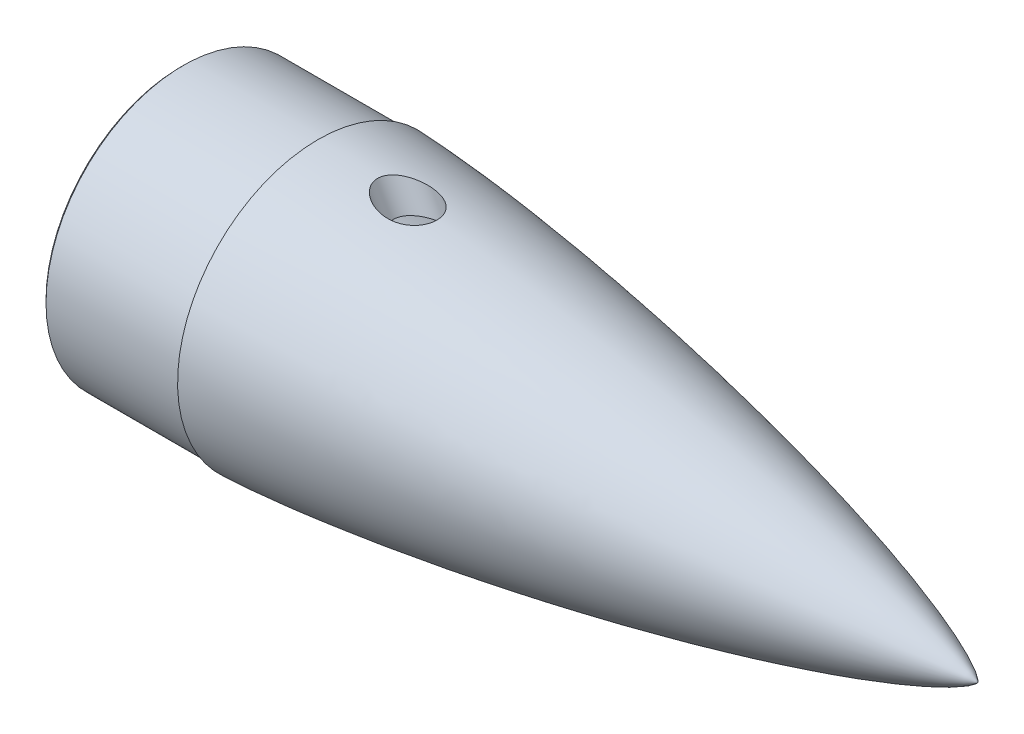
SolidWorks part; units mm, degrees
material "Plain Carbon Steel"
ref_plane "Front Plane" through (0, 0, 0) normal (0, 0, 1) x (1, 0, 0)
ref_plane "Top Plane" through (0, 0, 0) normal (0, 1, 0) x (1, 0, 0)
ref_plane "Right Plane" through (0, 0, 0) normal (1, 0, 0) x (0, 0, -1)
ref_axis "Axis1" through (46.9179, 0, 0) along (-1, 0, 0)
sketch "Sketch10" plane through (0, 0, 0) normal (0, 0, 1) x (1, 0, 0)
  line L1 (-1.0327, 0) -> (486.9547, 0) construction
  line L2 (11.1125, 81.9998) -> (11.1125, 67.4998)
  line L3 (11.1125, 81.9998) -> (-84.6045, 81.9998)
  line L4 (408.9673, 0) -> (368.9673, 0)
  line L5 (-84.6045, 81.9998) -> (-84.6045, 84.9998)
  line L6 (-84.6045, 84.9998) -> (0.3953, 84.9998)
  line L7 (0.3953, 84.9998) -> (0.3953, 86.9998)
  line L8 (11.1125, 67.4998) -> (129.3045, 67.4998)
  line L9 (46.9179, 0) -> (-46.1272, 0) construction
  spline S0 degree 4 poles (408.9673, 0) (408.9649, 0.0135) (408.958, 0.0399) (408.9365, 0.0905) (408.8922, 0.1741) (408.8263, 0.2756) (408.7217, 0.4158) (408.5611, 0.6051) (408.3056, 0.8724) (407.8697, 1.2753) (407.121, 1.8851) (405.8038, 2.8259) (403.4624, 4.2872) (399.3253, 6.5318) (392.4811, 9.7589) (380.6621, 14.628) (363.6372, 20.7117) (342.2152, 27.4765) (317.4285, 34.4976) (291.8793, 41.1048) (266.2105, 47.229) (240.4455, 52.9334) (214.5989, 58.2554) (188.6809, 63.2176) (165.9462, 67.2533) (146.422, 70.4938) (130.1279, 73.0449) (117.0786, 74.9942) (104.0155, 76.8485) (92.5733, 78.3845) (82.7571, 79.6356) (74.5713, 80.6322) (68.0193, 81.4008) (61.4637, 82.1394) (54.9047, 82.8464) (48.3422, 83.5199) (41.7761, 84.1578) (36.0275, 84.6822) (31.0979, 85.1052) (26.9883, 85.4387) (23.6997, 85.6932) (20.0858, 85.9584) (16.7199, 86.189) (13.6021, 86.387) (10.7327, 86.5546) (8.4366, 86.6787) (6.14, 86.7922) (4.1299, 86.8793) (2.4065, 86.9446) (1.2573, 86.979) (0.6827, 86.9949) (0.3953, 86.9998) knots 0 0 0 0 0 0.00013 0.00026 0.00052 0.0009 0.00128 0.001925 0.002882 0.004418 0.006927 0.011111 0.018279 0.030673 0.051704 0.083102 0.139909 0.202703 0.265496 0.32829 0.391083 0.453877 0.516671 0.579464 0.642258 0.673655 0.705051 0.736448 0.767845 0.799242 0.81494 0.830639 0.846337 0.862036 0.877734 0.893432 0.909131 0.924829 0.932678 0.940527 0.948377 0.956226 0.967169 0.972641 0.978113 0.983585 0.989056 0.994528 0.997264 1 1 1 1 1 construction
  spline S1 degree 4 poles (408.9673, 0) (408.9649, 0.0135) (408.958, 0.0399) (408.9365, 0.0905) (408.8922, 0.1741) (408.8263, 0.2756) (408.7217, 0.4158) (408.5611, 0.6051) (408.3056, 0.8724) (407.8697, 1.2753) (407.121, 1.8851) (405.8038, 2.8259) (403.4624, 4.2872) (399.3253, 6.5318) (392.4811, 9.7589) (380.6621, 14.628) (363.6372, 20.7117) (342.2152, 27.4765) (317.4285, 34.4976) (291.8793, 41.1048) (266.2105, 47.229) (240.4455, 52.9334) (214.5989, 58.2554) (188.6809, 63.2176) (165.9462, 67.2533) (146.422, 70.4938) (130.1279, 73.0449) (117.0786, 74.9942) (104.0155, 76.8485) (92.5733, 78.3845) (82.7571, 79.6356) (74.5713, 80.6322) (68.0193, 81.4008) (61.4637, 82.1394) (54.9047, 82.8464) (48.3422, 83.5199) (41.7761, 84.1578) (36.0275, 84.6822) (31.0979, 85.1052) (26.9883, 85.4387) (23.6997, 85.6932) (20.0858, 85.9584) (16.7199, 86.189) (13.6021, 86.387) (10.7327, 86.5546) (8.4366, 86.6787) (6.14, 86.7922) (4.1299, 86.8793) (2.4065, 86.9446) (1.2573, 86.979) (0.6827, 86.9949) (0.3953, 86.9998) knots 0 0 0 0 0 0.00013 0.00026 0.00052 0.0009 0.00128 0.001925 0.002882 0.004418 0.006927 0.011111 0.018279 0.030673 0.051704 0.083102 0.139909 0.202703 0.265496 0.32829 0.391083 0.453877 0.516671 0.579464 0.642258 0.673655 0.705051 0.736448 0.767845 0.799242 0.81494 0.830639 0.846337 0.862036 0.877734 0.893432 0.909131 0.924829 0.932678 0.940527 0.948377 0.956226 0.967169 0.972641 0.978113 0.983585 0.989056 0.994528 0.997264 1 1 1 1 1
  spline S2 degree 4 poles (368.9673, 0) (368.9653, 0.0123) (368.9594, 0.0365) (368.9406, 0.083) (368.9023, 0.1587) (368.8455, 0.2503) (368.7557, 0.3766) (368.6167, 0.5484) (368.3929, 0.7936) (368.0087, 1.1649) (367.3447, 1.7299) (366.1761, 2.6016) (364.0928, 3.96) (360.426, 6.0407) (354.4022, 9.0183) (344.043, 13.5077) (329.152, 19.1285) (310.4252, 25.3986) (288.7413, 31.9337) (266.3785, 38.1061) (243.9014, 43.8469) (221.332, 49.212) (198.684, 54.2345) (175.9669, 58.9343) (156.0346, 62.7717) (138.9133, 65.8645) (124.6221, 68.3077) (113.1754, 70.1797) (101.7151, 71.9664) (91.6754, 73.4517) (83.0615, 74.6659) (75.8775, 75.6363) (70.1269, 76.3867) (64.3728, 77.1101) (58.6152, 77.8049) (52.854, 78.4695) (47.0892, 79.1019) (42.0417, 79.6247) (37.7129, 80.0488) (34.1039, 80.385) (31.2157, 80.6428) (28.0648, 80.911) (24.6507, 81.1843) (21.4654, 81.4195) (18.5093, 81.6177) (16.0448, 81.767) (14.3191, 81.8612) (12.8395, 81.9336) (11.8527, 81.9739) (11.3593, 81.993) (11.1125, 81.9998) knots 0 0 0 0 0 0.000135 0.00027 0.00054 0.00092 0.001299 0.001947 0.002931 0.004512 0.007081 0.01138 0.018708 0.031424 0.052705 0.084103 0.14091 0.203703 0.266497 0.329291 0.392084 0.454878 0.517672 0.580465 0.643259 0.674656 0.706052 0.737449 0.768846 0.800243 0.815941 0.831639 0.847338 0.863036 0.878735 0.894433 0.910132 0.92583 0.933679 0.941528 0.949378 0.957227 0.96792 0.978613 0.98396 0.989307 0.994653 0.997327 1 1 1 1 1 construction
  spline S3 degree 4 poles (368.9673, 0) (368.9653, 0.0123) (368.9594, 0.0365) (368.9406, 0.083) (368.9023, 0.1587) (368.8455, 0.2503) (368.7557, 0.3766) (368.6167, 0.5484) (368.3929, 0.7936) (368.0087, 1.1649) (367.3447, 1.7299) (366.1761, 2.6016) (364.0928, 3.96) (360.426, 6.0407) (354.4022, 9.0183) (344.043, 13.5077) (329.152, 19.1285) (310.4252, 25.3986) (288.7413, 31.9337) (266.3785, 38.1061) (243.9014, 43.8469) (221.332, 49.212) (198.684, 54.2345) (175.9669, 58.9343) (156.0346, 62.7717) (141.5091, 65.3956) (132.6794, 66.9245) (129.5628, 67.4559) (129.3045, 67.4998) knots 0 0 0 0 0 0.000135 0.00027 0.00054 0.00092 0.001299 0.001947 0.002931 0.004512 0.007081 0.01138 0.018708 0.031424 0.052705 0.084103 0.14091 0.203703 0.266497 0.329291 0.392084 0.454878 0.517672 0.580465 0.643259 0.674656 0.677492 0.677492 0.677492 0.677492 0.677492
  dimension "D1" = 86.9998
  dimension "D2" = 3
  dimension "D3" = 410
  dimension "D4" = 84.9998
  dimension "D5" = 370
  dimension "D6" = 84.9998
  dimension "D7" = 19.5
  dimension "D8" = 118.192
revolve "Revolve1" add sketch "Sketch10" angle 360 about axis through (46.9179, 0, 0) along (-1, 0, 0)
chamfer "Chamfer1" distance 1.5 angle 45 1 edges at (-84.6045, 0, -84.9998)
ref_plane "Plane2" through (11.1125, 0, 0) normal (-1, 0, 0) x (0, 0, 1)
sketch "Sketch12" plane through (11.1125, 0, 0) normal (-1, 0, 0) x (0, 0, 1)
  line L0 (-81.9998, 0) -> (-67.4998, 0)
  circle A2 centre (0, 0) radius 81.9998 construction
  circle A3 centre (0, 0) radius 67.4998 construction
  circle A4 centre (-74.7498, 0) radius 4
  circle A5 centre (-37.3749, 64.7353) radius 4
  circle A6 centre (37.3749, 64.7353) radius 4
  circle A7 centre (74.7498, 0) radius 4
  circle A8 centre (37.3749, -64.7353) radius 4
  circle A9 centre (-37.3749, -64.7353) radius 4
  point P17 (-50.2998, -44.6412)
  point P25 (0, 0)
  dimension "D1" = 6
hole_wizard "Tap Drill for #1 Helicoil1" positions "Sketch17" profile "Sketch18" hole size "#1-64" standard "ANSI Inch"
sketch "Sketch17" plane through (11.1125, 0, 0) normal (-1, 0, 0) x (0, 0, 1)
  point P0 (-37.3749, 64.7353)
sketch "Sketch18" plane through (11.1125, 64.7353, -37.3749) normal (0, 1, 0) x (0, 0, 1)
  line L0 (0, 0) -> (0, 9.525)
  line L1 (0, 9.525) -> (3.3782, 9.525)
  line L2 (3.3782, 9.525) -> (3.3782, 0)
  line L5 (3.3782, 0) -> (0, 0)
  line L10 (0, 9.525) -> (-3.3782, 9.525) construction
  line L11 (0, -6.35) -> (0, 107.95) construction
  dimension "Hole Dia." = 6.7564
  dimension "Hole Depth" = 9.525
  dimension "Drill Angle" = 180
pattern_circular "CirPattern1" count 6 over 360 about axis through (11.1125, 0, 0) along (1, 0, 0) of "Tap Drill for #1 Helicoil1"
ref_plane "Plane3" through (0, 60, 0) normal (0, 1, 0) x (1, 0, 0)
sketch "Sketch20" plane through (0, 60, 0) normal (0, 1, 0) x (1, 0, 0)
  line L0 (46.9179, 0) -> (-46.1272, 0) construction
  line L1 (24.7702, 25) -> (64.7702, 25)
  line L2 (24.7702, 25) -> (24.7702, -15)
  line L3 (24.7702, -15) -> (64.7702, -15)
  line L4 (64.7702, 25) -> (64.7702, -15)
  line L5 (24.7702, 25) -> (64.7702, -15) construction
  line L6 (24.7702, -15) -> (64.7702, 25) construction
  point P4 (44.7702, 5)
  dimension "D1" = 40
  dimension "D2" = 15
  dimension "D3" = 40
extrude "Cut-Extrude3" [suppressed] cut sketch "Sketch20" along normal blind 12
sketch "Sketch22" plane through (0, 60, 0) normal (0, 1, 0) x (1, 0, 0)
  circle A0 centre (32, 6) radius 7.5
  dimension "D1" = 15
extrude "Cut-Extrude4" [suppressed] cut sketch "Sketch22" along normal through all
sketch "Sketch24" plane through (0, 60, 0) normal (0, 1, 0) x (1, 0, 0)
  line L0 (38.1988, 66.2764) -> (38.1988, 16.8548)
ref_plane "Plane4" through (-16.4311, 28.4594, 0) normal (-0.5, 0.866, 0) x (0, 0, 1)
sketch "Sketch26" plane through (-16.4311, 28.4594, 0) normal (-0.5, 0.866, 0) x (0, 0, 1)
  circle A0 centre (0, 89.5256) radius 15
extrude "Cut-Extrude5" cut sketch "Sketch26" against normal blind 50
extrude "Cut-Extrude6" cut sketch "Sketch26<2>" along normal blind 50
sketch "Sketch26<2>" plane through (-16.4311, 28.4594, 0) normal (-0.5, 0.866, 0) x (0, 0, 1) same geometry as "Sketch26"
equation "\"TubeDiameter\" = 6.250in"
